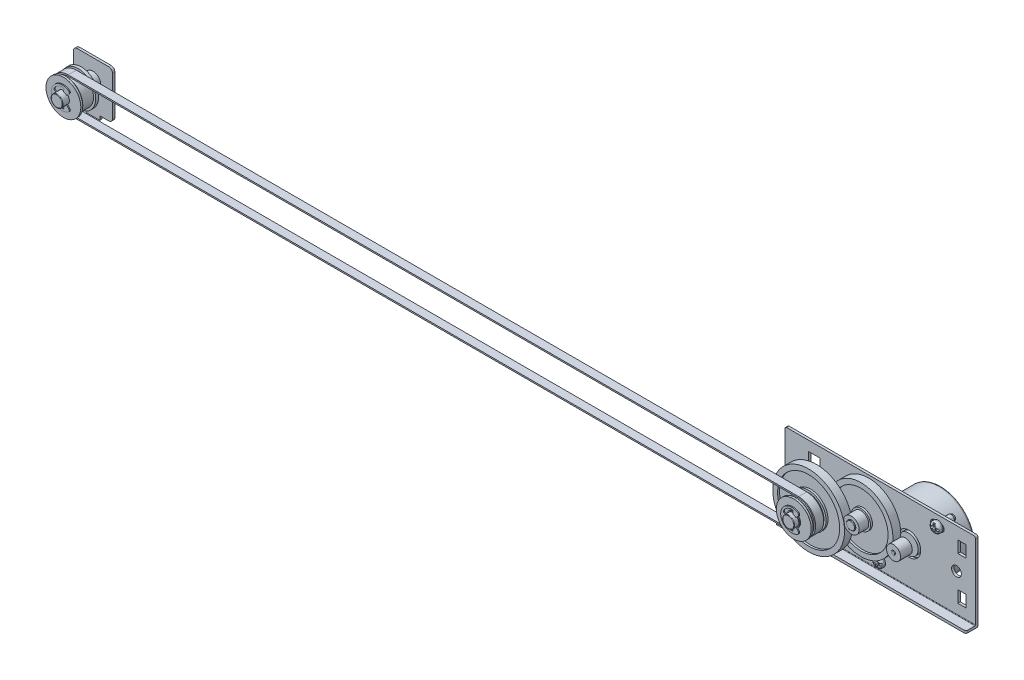
SolidWorks part; units mm, degrees
ref_plane "Plano frontal" through (0, 0, 0) normal (0, 0, 1) x (1, 0, 0)
ref_plane "Plano superior" through (0, 0, 0) normal (0, 1, 0) x (1, 0, 0)
ref_plane "Plano direito" through (0, 0, 0) normal (1, 0, 0) x (0, 0, -1)
sketch "Esboço1" plane through (0, 0, 0) normal (0, 0, 1) x (1, 0, 0)
  line L1 (48.7, 0.625) -> (-48.7, 0.625)
  line L2 (48.7, 0.625) -> (48.7, -0.625)
  line L3 (48.7, -0.625) -> (-48.7, -0.625)
  line L4 (-48.7, 0.625) -> (-48.7, -0.625)
  line L5 (48.7, 0.625) -> (-48.7, -0.625) construction
  line L6 (48.7, -0.625) -> (-48.7, 0.625) construction
  point P0 (0, 0)
  dimension "D1" = 97.4
  dimension "D2" = 1.25
extrude "Ressalto-extrusão1" add sketch "Esboço1" along normal blind 6.2
sketch "Esboço2" plane through (0, -0.625, 0) normal (0, 1, 0) x (1, 0, 0)
  line L0 (48.7, -6.2) -> (48.7, 0) construction
  line L1 (-48.7, 0) -> (48.7, 0)
  line L2 (-48.7, 0) -> (-48.7, -1.25)
  line L3 (-48.7, -1.25) -> (48.7, -1.25)
  line L4 (48.7, 0) -> (48.7, -1.25)
  dimension "D1" = 1.25
extrude "Ressalto-extrusão2" add sketch "Esboço2" along normal blind 40.6 contours L3 L4 L1 L2
fillet "Filete1" radius 1 4 edges at (48.7, 39.975, 0.625) (-48.7, 39.975, 0.625) (48.7, 0, 6.2) (-48.7, 0, 6.2)
sketch "Esboço3" plane through (0, 0, 1.25) normal (0, 0, 1) x (1, 0, 0)
  line L0 (27.7, 34.975) -> (30.7, 34.975) construction
  line L11 (39.7, 33.975) -> (43.7, 33.975)
  line L12 (39.7, 33.975) -> (39.7, 27.975)
  line L13 (39.7, 27.975) -> (43.7, 27.975)
  line L14 (43.7, 33.975) -> (43.7, 27.975)
  line L15 (39.7, 11.975) -> (43.7, 11.975)
  line L16 (39.7, 11.975) -> (39.7, 5.975)
  line L17 (39.7, 5.975) -> (43.7, 5.975)
  line L18 (43.7, 11.975) -> (43.7, 5.975)
  line L19 (-36.7, 12.975) -> (-30.7, 12.975)
  line L20 (-36.7, 12.975) -> (-36.7, 4.975)
  line L21 (-36.7, 4.975) -> (-30.7, 4.975)
  line L22 (-30.7, 12.975) -> (-30.7, 4.975)
  line L23 (27.7, 36.975) -> (30.7, 36.975)
  line L24 (27.7, 32.975) -> (30.7, 32.975)
  line L25 (0, 39.975) -> (0, 2.975) construction
  line L26 (-47.7, 39.975) -> (47.7, 39.975) construction
  line L27 (-47.7, 39.975) -> (47.7, 39.975) construction
  line L28 (-48.7, 38.975) -> (-48.7, 0.625) construction
  line L29 (-36.7, 34.975) -> (-30.7, 34.975)
  line L30 (-36.7, 34.975) -> (-36.7, 26.975)
  line L31 (-36.7, 26.975) -> (-30.7, 26.975)
  line L32 (-30.7, 34.975) -> (-30.7, 26.975)
  line L33 (48.7, 38.975) -> (48.7, 0.625) construction
  line L34 (48.7, 19.8) -> (0, 19.8) construction
  circle A5 centre (-43.7, 4.975) radius 2
  circle A6 centre (0, 4.975) radius 2
  circle A7 centre (38.95, 19.8) radius 2.5
  circle A8 centre (14.7, 19.8) radius 6
  arc A9 (27.7, 36.975) -> (27.7, 32.975) centre (27.7, 34.975) ccw
  arc A10 (30.7, 32.975) -> (30.7, 36.975) centre (30.7, 34.975) ccw
  point P22 (29.2, 34.975)
  point P33 (25.7, 34.975)
  point P34 (32.7, 34.975)
  dimension "D14" = 5
  dimension "D16" = 16
  dimension "D27" = 4
  dimension "D3" = 4
  dimension "D6" = 12
  dimension "D17" = 5
  dimension "D4" = 35
  dimension "D8" = 34
  dimension "D9" = 6
  dimension "D10" = 4
  dimension "D11" = 6
  dimension "D12" = 4
  dimension "D13" = 5
  dimension "D15" = 6
  dimension "D18" = 9.75
  dimension "D19" = 8
  dimension "D20" = 6
  dimension "D21" = 8
  dimension "D22" = 6
  dimension "D23" = 12
  dimension "D24" = 12
  dimension "D25" = 5
  dimension "D26" = 14
  dimension "D28" = 5
  dimension "D29" = 35
  dimension "D30" = 0
  dimension "D31" = 4
  dimension "D32" = 7
  dimension "D33" = 3
  dimension "D34" = 16
extrude "Corte-extrusão1" cut sketch "Esboço3" against normal blind 40.6
sketch "Esboço5" plane through (0, 0, 0) normal (0, 0, -1) x (-1, 0, 0)
  line L0 (-20.7, 19.8) -> (48.7, 19.8) construction
  line L1 (48.7, 38.975) -> (48.7, -0.625) construction
  line L2 (47.7, 39.975) -> (-47.7, 39.975) construction
  line L3 (48.7, 23.975) -> (48.7, 19.8) construction
  circle A0 centre (4.1, 23.975) radius 2
  circle A1 centre (25.7, 19.8) radius 3
  circle A2 centre (-14.7, 19.8) radius 6 construction
  dimension "D1" = 23
  dimension "6" = 6
  dimension "D2" = 4
  dimension "D3" = 16
  dimension "D4" = 44.6
sketch "Esboço6" plane through (0, 0, 0) normal (0, 0, -1) x (-1, 0, 0)
  circle A0 centre (25.7, 19.8) radius 3
  dimension "D1" = 6
extrude "Ressalto-extrusão3" add sketch "Esboço6" against normal blind 22.5
sketch "Esboço7" plane through (0, 0, 0) normal (0, 0, -1) x (-1, 0, 0)
  circle A0 centre (4.1, 23.975) radius 2.25
  dimension "D1" = 4.5
extrude "Ressalto-extrusão4" add sketch "Esboço7" against normal blind 12.3
fillet "Filete2" radius 0.25 2 edges at (-6.35, 23.975, 12.3) (-28.7, 19.8, 22.5)
sketch "Esboço12" plane through (0, 0, 0) normal (0, 0, 1) x (1, 0, 0)
  circle A0 centre (-4.1, 23.975) radius 4
  dimension "D1" = 8
extrude "Ressalto-extrusão7" add sketch "Esboço12" along normal blind 3
sketch "Esboço13" plane through (0, 0, 0) normal (0, 0, -1) x (-1, 0, 0)
  circle A0 centre (25.7, 19.8) radius 4.5
  dimension "D1" = 9
extrude "Ressalto-extrusão8" add sketch "Esboço13" against normal blind 8.1
sketch "Esboço8" plane through (0, 0, 3) normal (0, 0, 1) x (1, 0, 0)
  circle A0 centre (-4.1, 23.975) radius 16.365
  circle A1 centre (-4.1, 23.975) radius 2.3
  dimension "D1" = 32.73
  dimension "D2" = 4.6
extrude "Ressalto-extrusão5" add sketch "Esboço8" along normal blind 4
sketch "Esboço9" plane through (0, 0, 3) normal (0, 0, 1) x (1, 0, 0)
  circle A1 centre (-4.1, 23.975) radius 4
  circle A2 centre (-4.1, 23.975) radius 2.3
  dimension "D1" = 8
extrude "Ressalto-extrusão6" add sketch "Esboço9" along normal blind 8.9
sketch "Esboço10" plane through (0, 0, 7) normal (0, 0, 1) x (1, 0, 0)
  circle A0 centre (-4.1, 23.975) radius 4.9
  circle A1 centre (-4.1, 23.975) radius 13.865
  circle A2 centre (-4.1, 23.975) radius 16.365 construction
  dimension "D1" = 9.8
  dimension "D2" = 2.5
extrude "Corte-extrusão2" cut sketch "Esboço10" against normal blind 1
sketch "Esboço11" plane through (0, 0, 3) normal (0, 0, -1) x (-1, 0, 0)
  circle A1 centre (4.1, 23.975) radius 13.86
  circle A2 centre (4.1, 23.975) radius 4.9
extrude "Corte-extrusão3" cut sketch "Esboço11" against normal blind 1
sketch "Esboço14" plane through (0, 0, 8.1) normal (0, 0, 1) x (1, 0, 0)
  circle A0 centre (-25.7, 19.8) radius 18.34
  circle A1 centre (-25.7, 19.8) radius 3.1
  circle A2 centre (-25.7, 19.8) radius 3 construction
  dimension "D1" = 36.68
  dimension "D2" = 0.1
extrude "Ressalto-extrusão9" add sketch "Esboço14" along normal blind 4
sketch "Esboço15" plane through (0, 0, 8.1) normal (0, 0, 1) x (1, 0, 0)
  circle A0 centre (-25.7, 19.8) radius 7.8
  circle A1 centre (-25.7, 19.8) radius 3.1
  dimension "D1" = 15.6
extrude "Ressalto-extrusão10" add sketch "Esboço15" along normal blind 11.6
sketch "Esboço16" plane through (0, 0, 19.7) normal (0, 0, 1) x (1, 0, 0)
  circle A0 centre (-25.7, 19.8) radius 3.1
  circle A1 centre (-25.7, 19.8) radius 8.9
  dimension "D1" = 17.8
extrude "Ressalto-extrusão11" add sketch "Esboço16" against normal blind 1.5
chamfer "Chanfro1" distance 0.5 angle 45 1 edges at (-16.8, 19.8, 18.2)
sketch "Esboço17" plane through (0, 0, 19.7) normal (0, 0, 1) x (1, 0, 0)
  circle A0 centre (-25.7, 19.8) radius 3.1
  circle A1 centre (-25.7, 19.8) radius 3.5
  dimension "D1" = 7
extrude "Ressalto-extrusão12" add sketch "Esboço17" along normal blind 0.5
sketch "Esboço18" plane through (0, 0, 12.1) normal (0, 0, 1) x (1, 0, 0)
  circle A0 centre (-25.7, 19.8) radius 15.84
  circle A1 centre (-25.7, 19.8) radius 8.9
  circle A2 centre (-25.7, 19.8) radius 18.34 construction
  dimension "D1" = 2.5
  dimension "D2" = 17.8
extrude "Corte-extrusão4" cut sketch "Esboço18" against normal blind 1
sketch "Esboço19" plane through (0, 0, 8.1) normal (0, 0, -1) x (-1, 0, 0)
  circle A0 centre (25.7, 19.8) radius 8.9
  circle A1 centre (25.7, 19.8) radius 15.825
extrude "Corte-extrusão5" cut sketch "Esboço19" against normal blind 1
sketch "Esboço20" plane through (0, 0, 20.2) normal (0, 0, 1) x (1, 0, 0)
  line L0 (-28.3227, 20.6269) -> (-29.675, 21.0533)
  line L3 (-23.7555, 21.7445) -> (-22.4747, 23.0253)
  line L4 (-25.2225, 22.5082) -> (-24.9763, 23.9046)
  line L5 (-23.7555, 17.8555) -> (-22.4747, 16.5747)
  line L6 (-25.2225, 17.0918) -> (-24.9763, 15.6954)
  line L7 (-28.3227, 18.9731) -> (-29.675, 18.5467)
  arc A0 (-22.6425, 24.5746) -> (-22.6425, 15.0254) centre (-25.7, 19.8) ccw
  arc A1 (-25.4411, 24.4906) -> (-29.9802, 21.7362) centre (-25.7, 19.8) ccw
  arc A2 (-28.3227, 20.6269) -> (-28.3227, 18.9731) centre (-25.7, 19.8) ccw
  arc A3 (-23.7555, 21.7445) -> (-25.2225, 22.5082) centre (-25.7, 19.8) ccw
  arc A4 (-25.2225, 17.0918) -> (-23.7555, 17.8555) centre (-25.7, 19.8) ccw
  arc A5 (-29.9802, 17.8638) -> (-25.4411, 15.1094) centre (-25.7, 19.8) ccw
  arc A6 (-22.4747, 16.5747) -> (-22.6425, 15.0254) centre (-23.1818, 15.8675) cw
  arc A7 (-22.4747, 23.0253) -> (-22.6425, 24.5746) centre (-23.1818, 23.7325) ccw
  arc A8 (-25.4411, 15.1094) -> (-24.9763, 15.6954) centre (-25.4687, 15.6086) ccw
  arc A9 (-25.4411, 24.4906) -> (-24.9763, 23.9046) centre (-25.4687, 23.9914) cw
  arc A10 (-29.9802, 17.8638) -> (-29.675, 18.5467) centre (-29.5246, 18.0698) cw
  arc A11 (-29.9802, 21.7362) -> (-29.675, 21.0533) centre (-29.5246, 21.5302) ccw
  dimension "D2" = 1
  dimension "D3" = 0.5
  dimension "D1" = 35
  dimension "D4" = 35
  dimension "D5" = 35
extrude "Ressalto-extrusão13" add sketch "Esboço20" along normal blind 0.5
sketch "Esboço21" plane through (0, 0, 0) normal (0, 0, -1) x (-1, 0, 0)
  line L0 (-29.3939, 34.975) -> (0, 4.975) construction
  line L1 (3.3061, 4.975) -> (-3.6939, 4.975) construction
  line L2 (3.5952, 5.1615) -> (2.7796, 20.8817)
  line L3 (-13.4337, 37.4293) -> (-29.134, 38.5656)
  line L4 (0, 1.375) -> (-4.8727, 1.375)
  line L5 (-32.9939, 34.975) -> (-32.9939, 30.076)
  line L6 (-32.9939, 30.076) -> (-30.4878, 27.5182)
  line L7 (-7.4776, 4.0335) -> (-4.8727, 1.375)
  circle A2 centre (0, 4.975) radius 1.75
  circle A3 centre (-29.3939, 34.975) radius 1.75
  arc A4 (-30.4878, 27.5182) -> (-7.4776, 4.0335) centre (-14.6969, 19.975) ccw
  arc A5 (0, 1.375) -> (3.5952, 5.1615) centre (0, 4.975) ccw
  arc A7 (-29.134, 38.5656) -> (-32.9939, 34.975) centre (-29.3939, 34.975) ccw
  arc A9 (2.7796, 20.8817) -> (-13.4337, 37.4293) centre (-14.6969, 19.975) ccw
  dimension "D2" = 3.5
  dimension "D3" = 3.5
  dimension "D4" = 35
  dimension "D5" = 7.2
  dimension "D1" = 42
  dimension "D7" = 6
extrude "Ressalto-extrusão14" add sketch "Esboço21" along normal blind 0.92
sketch "Esboço23" plane through (0, 0, 0) normal (0, 0, 1) x (1, 0, 0)
  circle A0 centre (14.7, 19.8) radius 17.675
extrude "Ressalto-extrusão15" add sketch "Esboço23" against normal blind 15
fillet "Filete4" radius 1 1 edges at (32.375, 19.8, -15)
sketch "Esboço24" plane through (0, 0, -0.92) normal (0, 0, -1) x (-1, 0, 0)
  circle A0 centre (0, 4.975) radius 1.75
  circle A1 centre (0, 4.975) radius 2.05
  circle A2 centre (-29.3939, 34.975) radius 1.75
  circle A3 centre (-29.3939, 34.975) radius 2.05
  dimension "D1" = 0.3
  dimension "D2" = 0.3
extrude "Ressalto-extrusão16" add sketch "Esboço24" along normal blind 1
sketch "Esboço25" plane through (0, 0, -15) normal (0, 0, -1) x (-1, 0, 0)
  circle A0 centre (-14.7, 19.8) radius 2.5
  dimension "D1" = 5
extrude "Ressalto-extrusão17" add sketch "Esboço25" along normal blind 0.1
sketch "Esboço26" plane through (0, 0, -15.1) normal (0, 0, -1) x (-1, 0, 0)
  circle A0 centre (-14.7, 19.8) radius 1
  dimension "D1" = 2
extrude "Ressalto-extrusão18" add sketch "Esboço26" along normal blind 0.5
fillet "Filete6" radius 0.1 1 edges at (12.2, 19.8, -15.1)
sketch "Esboço27" plane through (0, 0, -15) normal (0, 0, 1) x (1, 0, 0)
  circle A0 centre (14.7, 19.8) radius 4.99
  dimension "D1" = 9.98
extrude "Ressalto-extrusão19" add sketch "Esboço27" along normal blind 16.57
sketch "Esboço28" plane through (0, 0, -15.6) normal (0, 0, -1) x (-1, 0, 0)
  circle A0 centre (-14.7, 19.8) radius 1
extrude "Ressalto-extrusão20" add sketch "Esboço28" against normal blind 25
fillet "Filete5" radius 0.25 2 edges at (13.7, 19.8, -15.6) (13.7, 19.8, 9.4)
ref_plane "Plano2" through (0, 0, 9.15) normal (0, 0, 1) x (1, 0, 0)
sketch "Esboço29" plane through (0, 0, 9.15) normal (0, 0, 1) x (1, 0, 0)
  circle A0 centre (14.7, 19.8) radius 3.59
  dimension "D1" = 7.18
extrude "Ressalto-extrusão21" add sketch "Esboço29" against normal blind 6
sketch "Esboço30" plane through (0, 0, 1.25) normal (0, 0, 1) x (1, 0, 0)
  circle A0 centre (0, 4.975) radius 2.7
  circle A1 centre (29.3939, 34.975) radius 2.7
  dimension "D1" = 5.4
  dimension "D2" = 5.4
extrude "Ressalto-extrusão22" add sketch "Esboço30" along normal blind 2
fillet "Filete7" radius 1.4 2 edges at (2.7, 4.975, 3.25) (32.0939, 34.975, 3.25)
sketch "Esboço31" plane through (0, 0, 3.25) normal (0, 0, 1) x (1, 0, 0)
  line L1 (29.0939, 37.175) -> (29.6939, 37.175)
  line L2 (28.8939, 36.975) -> (28.8939, 35.975)
  line L3 (29.0939, 32.775) -> (29.6939, 32.775)
  line L4 (29.8939, 36.975) -> (29.8939, 35.975)
  line L7 (31.3939, 35.475) -> (30.3939, 35.475)
  line L8 (31.5939, 35.275) -> (31.5939, 34.675)
  line L9 (31.3939, 34.475) -> (30.3939, 34.475)
  line L10 (27.1939, 35.275) -> (27.1939, 34.675)
  line L15 (28.8939, 33.975) -> (28.8939, 32.975)
  line L17 (29.8939, 33.975) -> (29.8939, 32.975)
  line L18 (28.3939, 35.475) -> (27.3939, 35.475)
  line L19 (28.3939, 34.475) -> (27.3939, 34.475)
  line L42 (-0.1421, 7.325) -> (0.4579, 7.325)
  line L43 (-0.3421, 7.125) -> (-0.3421, 6.125)
  line L44 (-0.1421, 2.925) -> (0.4579, 2.925)
  line L45 (0.6579, 7.125) -> (0.6579, 6.125)
  line L46 (2.1579, 5.625) -> (1.1579, 5.625)
  line L47 (2.3579, 5.425) -> (2.3579, 4.825)
  line L48 (2.1579, 4.625) -> (1.1579, 4.625)
  line L49 (-2.0421, 5.425) -> (-2.0421, 4.825)
  line L50 (-0.3421, 4.125) -> (-0.3421, 3.125)
  line L51 (0.6579, 4.125) -> (0.6579, 3.125)
  line L52 (-0.8421, 5.625) -> (-1.8421, 5.625)
  line L53 (-0.8421, 4.625) -> (-1.8421, 4.625)
  arc A0 (29.8939, 33.975) -> (30.3939, 34.475) centre (30.3939, 33.975) cw
  arc A1 (28.8939, 33.975) -> (28.3939, 34.475) centre (28.3939, 33.975) ccw
  arc A2 (29.8939, 35.975) -> (30.3939, 35.475) centre (30.3939, 35.975) ccw
  arc A3 (28.8939, 35.975) -> (28.3939, 35.475) centre (28.3939, 35.975) cw
  arc A4 (28.8939, 32.975) -> (29.0939, 32.775) centre (29.0939, 32.975) ccw
  arc A5 (29.6939, 32.775) -> (29.8939, 32.975) centre (29.6939, 32.975) ccw
  arc A6 (31.5939, 34.675) -> (31.3939, 34.475) centre (31.3939, 34.675) cw
  arc A7 (31.3939, 35.475) -> (31.5939, 35.275) centre (31.3939, 35.275) cw
  arc A8 (29.6939, 37.175) -> (29.8939, 36.975) centre (29.6939, 36.975) cw
  arc A9 (29.0939, 37.175) -> (28.8939, 36.975) centre (29.0939, 36.975) ccw
  arc A10 (27.3939, 35.475) -> (27.1939, 35.275) centre (27.3939, 35.275) ccw
  arc A11 (27.3939, 34.475) -> (27.1939, 34.675) centre (27.3939, 34.675) cw
  circle A24 centre (29.3939, 34.975) radius 1.3 construction
  arc A37 (0.6579, 4.125) -> (1.1579, 4.625) centre (1.1579, 4.125) cw
  arc A38 (-0.3421, 4.125) -> (-0.8421, 4.625) centre (-0.8421, 4.125) ccw
  arc A39 (0.6579, 6.125) -> (1.1579, 5.625) centre (1.1579, 6.125) ccw
  arc A40 (-0.3421, 6.125) -> (-0.8421, 5.625) centre (-0.8421, 6.125) cw
  arc A41 (-0.3421, 3.125) -> (-0.1421, 2.925) centre (-0.1421, 3.125) ccw
  arc A42 (0.4579, 2.925) -> (0.6579, 3.125) centre (0.4579, 3.125) ccw
  arc A43 (2.3579, 4.825) -> (2.1579, 4.625) centre (2.1579, 4.825) cw
  arc A44 (2.1579, 5.625) -> (2.3579, 5.425) centre (2.1579, 5.425) cw
  arc A45 (0.4579, 7.325) -> (0.6579, 7.125) centre (0.4579, 7.125) cw
  arc A46 (-0.1421, 7.325) -> (-0.3421, 7.125) centre (-0.1421, 7.125) ccw
  arc A47 (-1.8421, 5.625) -> (-2.0421, 5.425) centre (-1.8421, 5.425) ccw
  arc A48 (-1.8421, 4.625) -> (-2.0421, 4.825) centre (-1.8421, 4.825) cw
  point P0 (0, 4.975)
  point P6 (29.3939, 34.975)
  point P19 (28.8939, 34.475)
  point P24 (28.8939, 35.475)
  point P27 (28.8939, 32.775)
  point P30 (29.8939, 32.775)
  point P33 (31.5939, 34.475)
  point P36 (31.5939, 35.475)
  point P39 (29.8939, 37.175)
  point P44 (27.1939, 35.475)
  point P128 (0.1579, 5.125)
  point P133 (0.1579, 5.125)
  dimension "D5" = 0.5
  dimension "D6" = 0.2
  dimension "D9" = 0.5
  dimension "D10" = 0.2
  dimension "D1" = 4.4
  dimension "D2" = 4.4
  dimension "D3" = 1
  dimension "D4" = 1
extrude "Corte-extrusão6" cut sketch "Esboço31" against normal blind 1.4
sketch "Esboço32" plane through (0, 0, 1.25) normal (0, 0, -1) x (-1, 0, 0)
  circle A0 centre (0, 4.975) radius 1.75
  circle A1 centre (-29.3939, 34.975) radius 1.75
extrude "Ressalto-extrusão23" add sketch "Esboço32" along normal blind 7.8
chamfer "Chanfro2" distance 1 angle 25 2 edges at (-1.75, 4.975, -6.55) (27.6439, 34.975, -6.55) first distance on face at (-1.75, 4.975, -1.92) first distance on face at (27.6439, 34.975, -1.92)
sketch "Esboço33" plane through (0, 0, -0.92) normal (0, 0, -1) x (-1, 0, 0)
  line L1 (3.2243, 12.8461) -> (4.2922, 22.7889)
  line L2 (4.2922, 22.7889) -> (2.6901, 22.961)
  line L3 (3.2243, 12.8461) -> (1.6222, 13.0182)
  arc A4 (1.6222, 13.0182) -> (2.6901, 22.961) centre (-14.7, 19.8) ccw
  arc A7 (1.6222, 13.0182) -> (2.6901, 22.961) centre (-14.7, 19.8) ccw
  arc M4 (2.9127, 18.3164) -> (-7.2301, 3.781) centre (-14.7, 19.8) cw
  line M8 (3.5952, 5.1615) -> (2.9127, 18.3164)
  dimension "D1" = 10
  dimension "D2" = 90
extrude "Ressalto-extrusão24" add sketch "Esboço33" along normal blind 10 contours A4 L3 L1 L2 M8 | L3 M8 M4 region at (-3.4256, 19.3944, -0.92) region at (-2.6269, 14.5261, -0.92)
sketch "Esboço34" plane through (-1.8235, -0.1959, 0) normal (-0.9943, -0.1068, 0) x (0, 0, 1)
  line L0 (-5.92, 23.117) -> (-5.92, 13.117) construction
  line L1 (-10.92, 23.117) -> (-0.92, 23.117) construction
  line L2 (-10.92, 13.117) -> (-0.92, 13.117) construction
  circle A0 centre (-5.92, 18.117) radius 2
  dimension "D1" = 4
extrude "Ressalto-extrusão25" add sketch "Esboço34" along normal blind 5
sketch "Esboço35" plane through (0, 0, 12.1) normal (0, 0, 1) x (1, 0, 0)
  line L0 (-48.7, 38.975) -> (-48.7, 0.625) construction
  circle A0 centre (-398.7, 19.8) radius 7.8
  point P2 (-25.7, 19.8)
  dimension "D1" = 15.6
  dimension "D2" = 350
  dimension "D3" = 0
extrude "Ressalto-extrusão26" add sketch "Esboço35" along normal blind 7.6 separate body
sketch "Esboço37" plane through (0, 0, 19.7) normal (0, 0, 1) x (1, 0, 0)
  circle A0 centre (-398.7, 19.8) radius 8.9
  dimension "D1" = 17.8
extrude "Ressalto-extrusão27" add sketch "Esboço37" against normal blind 1.5
chamfer "Chanfro3" distance 0.5 angle 45 1 edges at (-389.8, 19.8, 18.2)
sketch "Esboço38" plane through (0, 0, 12.1) normal (0, 0, -1) x (-1, 0, 0)
  circle A0 centre (398.7, 19.8) radius 8.9
extrude "Ressalto-extrusão28" add sketch "Esboço38" along normal blind 1.5
sketch "Esboço39" plane through (0, 0, 19.7) normal (0, 0, 1) x (1, 0, 0)
  circle A0 centre (-398.7, 19.8) radius 3.05
  dimension "D1" = 6.1
extrude "Corte-extrusão7" cut sketch "Esboço39" against normal blind 35.5 and the other way blind 16
sketch "Esboço40" plane through (0, 0, 10.6) normal (0, 0, -1) x (-1, 0, 0)
  circle A0 centre (398.7, 19.8) radius 4
  dimension "D1" = 8
extrude "Ressalto-extrusão29" add sketch "Esboço40" along normal blind 6
sketch "Esboço41" plane through (0, 0, 4.6) normal (0, 0, -1) x (-1, 0, 0)
  circle A0 centre (398.7, 19.8) radius 3
  dimension "D1" = 6
extrude "Ressalto-extrusão30" add sketch "Esboço41" against normal blind 18.5
fillet "Filete8" radius 0.25 1 edges at (-401.7, 19.8, 23.1)
sketch "Esboço42" plane through (0, 0, 19.7) normal (0, 0, 1) x (1, 0, 0)
  line L6 (-401.3227, 20.6269) -> (-402.675, 21.0533)
  line L7 (-396.7555, 21.7445) -> (-395.4747, 23.0253)
  line L8 (-398.2225, 22.5082) -> (-397.9763, 23.9046)
  line L9 (-396.7555, 17.8555) -> (-395.4747, 16.5747)
  line L10 (-398.2225, 17.0918) -> (-397.9763, 15.6954)
  line L11 (-401.3227, 18.9731) -> (-402.675, 18.5467)
  arc A12 (-395.6425, 24.5746) -> (-395.6425, 15.0254) centre (-398.7, 19.8) ccw
  arc A13 (-398.4411, 24.4906) -> (-402.9802, 21.7362) centre (-398.7, 19.8) ccw
  arc A14 (-401.3227, 20.6269) -> (-401.3227, 18.9731) centre (-398.7, 19.8) ccw
  arc A15 (-396.7555, 21.7445) -> (-398.2225, 22.5082) centre (-398.7, 19.8) ccw
  arc A16 (-398.2225, 17.0918) -> (-396.7555, 17.8555) centre (-398.7, 19.8) ccw
  arc A17 (-402.9802, 17.8638) -> (-398.4411, 15.1094) centre (-398.7, 19.8) ccw
  arc A18 (-395.4747, 16.5747) -> (-395.6425, 15.0254) centre (-396.1818, 15.8675) cw
  arc A19 (-395.4747, 23.0253) -> (-395.6425, 24.5746) centre (-396.1818, 23.7325) ccw
  arc A20 (-398.4411, 15.1094) -> (-397.9763, 15.6954) centre (-398.4687, 15.6086) ccw
  arc A21 (-398.4411, 24.4906) -> (-397.9763, 23.9046) centre (-398.4687, 23.9914) cw
  arc A22 (-402.9802, 17.8638) -> (-402.675, 18.5467) centre (-402.5246, 18.0698) cw
  arc A23 (-402.9802, 21.7362) -> (-402.675, 21.0533) centre (-402.5246, 21.5302) ccw
  point P0 (-398.7, 19.8)
  dimension "D4" = 1
  dimension "D5" = 0.5
  dimension "D1" = 35
  dimension "D2" = 35
  dimension "D3" = 35
extrude "Ressalto-extrusão31" add sketch "Esboço42" along normal blind 0.5
sketch "Esboço43" plane through (0, 0, 4.6) normal (0, 0, -1) x (-1, 0, 0)
  line L0 (402.2, 5.8) -> (402.2, 3.8)
  line L1 (408.7, 29.8) -> (388.7, 29.8)
  line L2 (408.7, 29.8) -> (408.7, 5.8)
  line L3 (408.7, 5.8) -> (402.2, 5.8)
  line L4 (388.7, 29.8) -> (388.7, 5.8)
  line L5 (395.2, 5.8) -> (388.7, 5.8)
  line L6 (408.7, 19.8) -> (388.7, 19.8) construction
  line L9 (395.2, 3.8) -> (402.2, 3.8)
  line L11 (398.7, 29.8) -> (398.7, 19.8) construction
  line L14 (395.2, 5.8) -> (395.2, 3.8)
  point P0 (398.7, 19.8)
  dimension "D1" = 20
  dimension "D2" = 24
  dimension "D4" = 7
  dimension "D5" = 26
extrude "Ressalto-extrusão32" add sketch "Esboço43" along normal blind 1.2 contours L1 L4 L5 L14 L9 L0 L3 L2
fillet "Filete9" radius 2 4 edges at (-408.7, 5.8, 4) (-388.7, 5.8, 4) (-388.7, 29.8, 4) (-408.7, 29.8, 4)
fillet "Filete10" radius 0.3 2 edges at (-402.2, 5.8, 4) (-395.2, 5.8, 4)
ref_plane "Plano3" through (0, 0, 13.1) normal (0, 0, 1) x (1, 0, 0)
sketch "Esboço44" plane through (0, 0, 13.1) normal (0, 0, 1) x (1, 0, 0)
  line L0 (-398.7, 19.8) -> (-25.7, 19.8) construction
  line L1 (-398.7, 27.8) -> (-25.7, 27.8)
  line L2 (-398.7, 11.8) -> (-25.7, 11.8)
  line L3 (-398.7, 28.5) -> (-25.7, 28.5)
  line L4 (-398.7, 11.1) -> (-25.7, 11.1)
  arc A0 (-398.7, 27.8) -> (-398.7, 11.8) centre (-398.7, 19.8) ccw
  arc A1 (-25.7, 11.8) -> (-25.7, 27.8) centre (-25.7, 19.8) ccw
  circle A2 centre (-25.7, 19.8) radius 7.8 construction
  arc A3 (-25.7, 11.1) -> (-25.7, 28.5) centre (-25.7, 19.8) ccw
  arc A4 (-398.7, 28.5) -> (-398.7, 11.1) centre (-398.7, 19.8) ccw
  point P4 (-212.2, 19.8)
  dimension "D1" = 8
  dimension "D2" = 0.7
extrude "Ressalto-extrusão33" add sketch "Esboço44" along normal blind 4.15
sketch "Esboço45" plane through (0, 0, 3.4) normal (0, 0, -1) x (-1, 0, 0)
  line L0 (398.7, 3.8) -> (398.7, 29.8) construction
  line L1 (395.2, 3.8) -> (402.2, 3.8) construction
  line L2 (406.7, 29.8) -> (390.7, 29.8) construction
  line L4 (388.7, 27.8) -> (388.7, 7.8) construction
  line L5 (388.7, 17.8) -> (408.7, 17.8) construction
  line L6 (408.7, 27.8) -> (408.7, 7.8) construction
fillet "Filete11" radius 0.5 1 edges at (0, -0.625, 0)
fillet "Filete12" radius 0.25 1 edges at (0, 0.625, 1.25)
